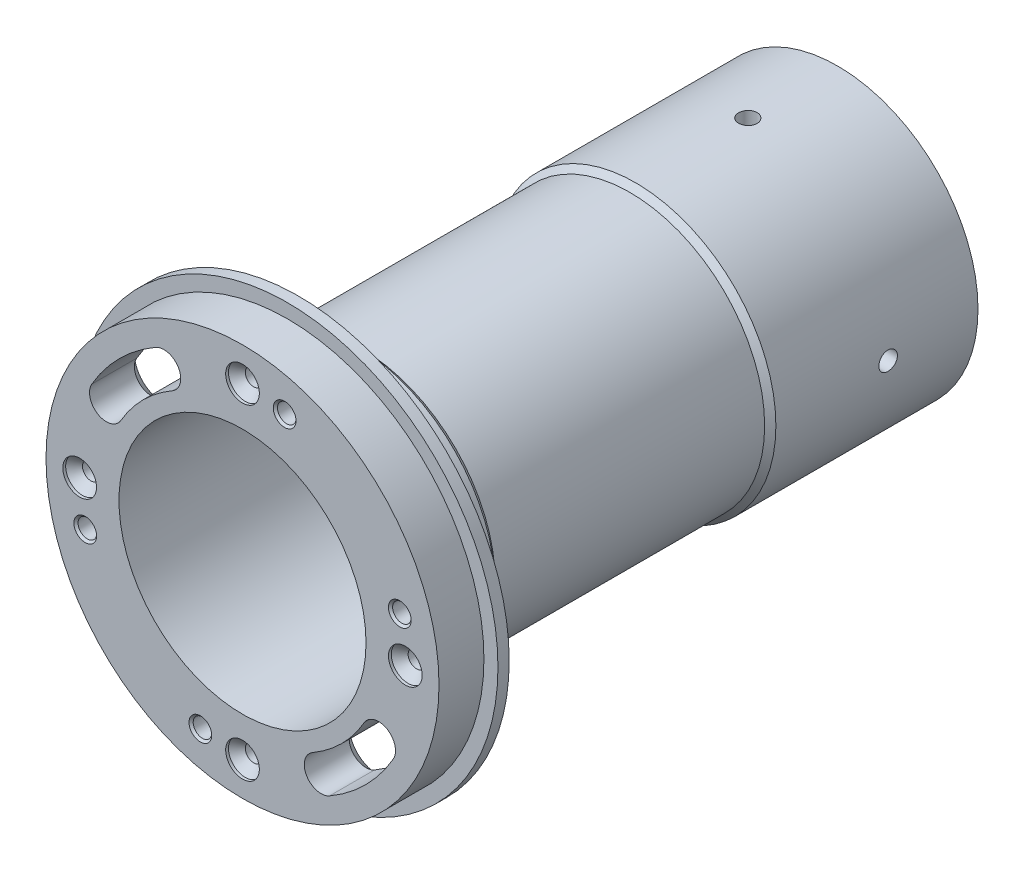
SolidWorks part; units mm, degrees
material "6061 合金"
ref_plane "前视基准面" through (0, 0, 0) normal (0, 0, 1) x (1, 0, 0)
ref_plane "上视基准面" through (0, 0, 0) normal (0, 1, 0) x (1, 0, 0)
ref_plane "右视基准面" through (0, 0, 0) normal (1, 0, 0) x (0, 0, -1)
sketch "草图1" plane through (0, 0, 0) normal (0, 1, 0) x (1, 0, 0)
  line L1 (37.5, 0) -> (37.5, 2)
  line L2 (37.5, 2) -> (25, 2)
  line L3 (25, 2) -> (25, 12)
  line L4 (25, 98) -> (22, 98)
  line L5 (22, 98) -> (22, 0)
  line L6 (0, 0) -> (0, 11.7715) construction
  line L8 (22, 0) -> (37.5, 0)
  line L10 (25, 62) -> (24, 62)
  line L12 (25, 12) -> (24, 12)
  line L13 (24, 62) -> (24, 12)
  line L14 (25, 62) -> (25, 98)
  dimension "D1" = 44
  dimension "D2" = 50
  dimension "D3" = 2
  dimension "D4" = 75
  dimension "D5" = 96
  dimension "D6" = 2
  dimension "D7" = 10
  dimension "D8" = 50
revolve "旋转1" add sketch "草图1" angle 360 about L6
sketch "草图5" plane through (0, 0, 0) normal (0, 0, 1) x (1, 0, 0)
  circle A0 centre (0, 0) radius 35
  circle A25 centre (0, 0) radius 22 construction
  circle A26 centre (0, 0) radius 22
  dimension "D1" = 70
extrude "凸台-拉伸1" add sketch "草图5" along normal blind 8
hole_wizard "M4 螺纹孔3" [suppressed] positions "草图3" profile "草图4" tap size "M4" standard "GB"
sketch "草图3" [suppressed] plane through (0, 0, 8) normal (0, 0, -1) x (-1, 0, 0)
  circle A0 centre (0, 0) radius 29 construction
  point P0 (29, 0)
  point P10 (0, -29)
  point P11 (-29, 0)
  point P12 (0, 29)
  dimension "D1" = 4
  dimension "D2" = 58
sketch "草图4" plane through (-29, 0, 8) normal (1, 0, 0) x (0, -1, 0)
  line L0 (0, 0) -> (0, 100)
  line L1 (0, 100) -> (1.65, 100)
  line L2 (1.65, 100) -> (1.65, 0)
  line L5 (1.65, 0) -> (0, 0)
  line L11 (0, -6.35) -> (0, 107.95) construction
  dimension "通孔螺纹孔钻头直径" = 3.3
  dimension "通孔螺纹孔钻头深度" = 100
cosmetic thread "孔螺蚊线14" parameters "D2"=4
cosmetic thread "孔螺蚊线15" parameters "D2"=4
cosmetic thread "孔螺蚊线16" parameters "D2"=4
cosmetic thread "孔螺蚊线17" parameters "D2"=4
hole_wizard "M4 螺纹孔2" positions "草图8" profile "草图9" tap size "M4" standard "GB"
sketch "草图8" plane through (0, 0, 0) normal (0, 1, 0) x (1, 0, 0)
  line L2 (25, 98) -> (-25, 98) construction
  point P0 (0, 82)
  dimension "D1" = 16
sketch "草图9" plane through (0, 0, -82) normal (1, 0, 0) x (0, 0, -1)
  line L0 (0, 0) -> (0, 37.5)
  line L1 (0, 37.5) -> (1.65, 37.5)
  line L2 (1.65, 37.5) -> (1.65, 0)
  line L5 (1.65, 0) -> (0, 0)
  line L11 (0, -6.35) -> (0, 107.95) construction
  dimension "通孔螺纹孔钻头直径" = 3.3
  dimension "通孔螺纹孔钻头深度" = 37.5
cosmetic thread "孔螺蚊线18" parameters "D1"=0, "D2"=4.3
sketch "草图2" plane through (0, 0, -2) normal (0, 0, -1) x (-1, 0, 0)
  arc A5 (-24.2487, 14) -> (-14, 24.2487) centre (0, 0) cw construction
  arc A6 (-15.5, 26.8468) -> (-26.8468, 15.5) centre (0, 0) ccw construction
  arc A7 (-12.5, 21.6506) -> (-21.6506, 12.5) centre (0, 0) ccw construction
  arc A8 (-12.5, 21.6506) -> (-15.5, 26.8468) centre (-14, 24.2487) ccw construction
  arc A9 (-26.8468, 15.5) -> (-21.6506, 12.5) centre (-24.2487, 14) ccw construction
  arc A15 (14, 24.2487) -> (24.2487, 14) centre (0, 0) cw construction
  arc A42 (26.8468, 15.5) -> (15.5, 26.8468) centre (0, 0) ccw
  arc A43 (21.6506, 12.5) -> (12.5, 21.6506) centre (0, 0) ccw
  arc A44 (21.6506, 12.5) -> (26.8468, 15.5) centre (24.2487, 14) ccw
  arc A45 (15.5, 26.8468) -> (12.5, 21.6506) centre (14, 24.2487) ccw
  arc A46 (24.2487, -14) -> (14, -24.2487) centre (0, 0) cw construction
  arc A47 (15.5, -26.8468) -> (26.8468, -15.5) centre (0, 0) ccw construction
  arc A48 (12.5, -21.6506) -> (21.6506, -12.5) centre (0, 0) ccw construction
  arc A49 (12.5, -21.6506) -> (15.5, -26.8468) centre (14, -24.2487) ccw construction
  arc A50 (26.8468, -15.5) -> (21.6506, -12.5) centre (24.2487, -14) ccw construction
  arc A51 (-14, -24.2487) -> (-24.2487, -14) centre (0, 0) cw construction
  arc A52 (-26.8468, -15.5) -> (-15.5, -26.8468) centre (0, 0) ccw
  arc A53 (-21.6506, -12.5) -> (-12.5, -21.6506) centre (0, 0) ccw
  arc A54 (-21.6506, -12.5) -> (-26.8468, -15.5) centre (-24.2487, -14) ccw
  arc A55 (-15.5, -26.8468) -> (-12.5, -21.6506) centre (-14, -24.2487) ccw
  circle A56 centre (0, 0) radius 29 construction
  circle A57 centre (0, 29) radius 1.5
  circle A58 centre (29, 0) radius 1.5
  circle A59 centre (0, -29) radius 1.5
  circle A60 centre (-29, 0) radius 1.5
  point P13 (-19.799, 19.799)
  point P18 (19.799, 19.799)
  point P27 (19.799, -19.799)
  point P36 (-19.799, -19.799)
  dimension "D1" = 58
  dimension "D2" = 3
  dimension "D3" = 25
  dimension "D4" = 31
  dimension "D5" = 30
  dimension "D6" = 4
extrude "切除-拉伸1" cut sketch "草图2" against normal through all
ref_plane "基准面1" through (0, 0, 0) normal (0.7071, 0.7071, 0) x (0, 0, -1)
sketch "草图10" plane through (0, 0, 0) normal (0.7071, 0.7071, 0) x (0, 0, -1)
  line L0 (24.5, 0) -> (69.5, 0) construction
  line L1 (24.5, 12.5) -> (69.5, 12.5)
  line L2 (24.5, -12.5) -> (69.5, -12.5)
  line L3 (2, -25) -> (2, 25) construction
  arc A0 (24.5, 12.5) -> (24.5, -12.5) centre (24.5, 0) ccw
  arc A1 (69.5, -12.5) -> (69.5, 12.5) centre (69.5, 0) ccw
  point P3 (47, 0)
  point P8 (12, 0)
  point P9 (82, 0)
  dimension "D1" = 70
  dimension "D2" = 10
  dimension "D3" = 25
extrude "切除-拉伸2" [suppressed] cut sketch "草图10" along normal through all
pattern_circular "阵列(圆周)1" count 4 over 360 of "切除-拉伸2", "M4 螺纹孔2"
hole_wizard "M4 螺纹孔4" positions "草图12" profile "草图13" tap size "M4" standard "GB"
sketch "草图12" plane through (0, 0, 8) normal (0, 0, 1) x (1, 0, 0)
  line L0 (0, 29) -> (0, 0) construction
  line L1 (0, 0) -> (7.5058, 28.0118) construction
  line L5 (0, 0) -> (23.7639, 23.7639) construction
  circle A0 centre (0, 0) radius 29 construction
  point P0 (7.5058, 28.0118)
  point P32 (28.0118, 7.5058)
  point P34 (-7.5058, -28.0118)
  point P35 (-28.0118, -7.5058)
  point P47 (-20.5061, 20.5061)
  point P48 (20.5061, -20.5061)
  dimension "D1" = 30
  dimension "D2" = 45
  dimension "D3" = 6
sketch "草图13" plane through (7.5058, 28.0118, 8) normal (1, 0, 0) x (0, -1, 0)
  line L0 (0, 0) -> (0, 106)
  line L1 (0, 106) -> (1.65, 106)
  line L2 (1.65, 106) -> (1.65, 0.375)
  line L3 (1.65, 0.375) -> (2.025, 0)
  line L5 (2.025, 0) -> (0, 0)
  line L6 (-1.65, 0.375) -> (-2.025, 0) construction
  line L11 (0, -6.35) -> (0, 107.95) construction
  dimension "通孔螺纹孔钻头直径" = 3.3
  dimension "通孔螺纹孔钻头深度" = 106
  dimension "近端锥形沉头孔直径" = 4.05
  dimension "近端锥形沉头孔角度" = 90
cosmetic thread "孔螺蚊线19" parameters "D2"=4
cosmetic thread "孔螺蚊线20" parameters "D2"=4
cosmetic thread "孔螺蚊线21" parameters "D2"=4
cosmetic thread "孔螺蚊线22" parameters "D2"=4
hole_wizard "孔1" positions "草图14" profile "草图15" legacy end condition through all
sketch "草图14" plane through (0, 0, 8) normal (0, 0, 1) x (1, 0, 0)
  point P0 (-29, 0)
  point P3 (0, -29)
  point P6 (29, 0)
  point P9 (0, 29)
sketch "草图15" plane through (-29, 0, 8) normal (1, 0, 0) x (0, -1, 0)
  line L0 (0, 0) -> (0, 106)
  line L1 (0, 106) -> (1.5, 106)
  line L2 (1.5, 106) -> (1.5, 2)
  line L3 (1.5, 2) -> (3, 0.5)
  line L4 (3, 0.5) -> (3, 0)
  line L5 (3, 0) -> (0, 0)
  line L6 (0, -6.13) -> (0, 109.2824) construction
  line L7 (-1.5, 2) -> (-3, 0.5) construction
  line L8 (0, 106) -> (-1.5, 106) construction
  dimension "直径" = 3
  dimension "深度" = 106
  dimension "沉头坑直径" = 6
  dimension "沉头坑深度" = 0.5
  dimension "导头角度" = 90
chamfer "倒角1" distance 2 angle 45 6 edges at (25.7487, -11.4019, -2) (11.4019, -25.7487, -2) (21.9203, -21.9203, -2) (-25.7487, 11.4019, -2) (-11.4019, 25.7487, -2) (-21.9203, 21.9203, -2)
chamfer "倒角2" distance 1 angle 45 2 edges at (24, 0, -62) (24, 0, -12)
